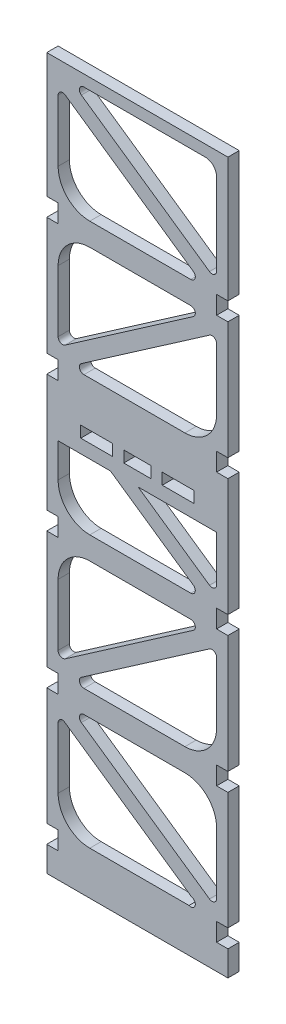
SolidWorks part; units mm, degrees
material "Balsa"
ref_plane "Front Plane" through (0, 0, 0) normal (0, 0, 1) x (1, 0, 0)
ref_plane "Top Plane" through (0, 0, 0) normal (0, 1, 0) x (1, 0, 0)
ref_plane "Right Plane" through (0, 0, 0) normal (1, 0, 0) x (0, 0, -1)
sketch "Model" plane through (0, 0, 0) normal (0, 0, 1) x (1, 0, 0)
  line L0 (77.47, 87.63) -> (20.8312, 87.63)
  line L1 (95.25, 35.3278) -> (95.25, 69.85)
  line L2 (19.3854, 83.0016) -> (91.2642, 33.2394)
  line L3 (6.35, 146.05) -> (6.35, 111.5278)
  line L4 (80.7688, 163.83) -> (24.13, 163.83)
  line L5 (10.3358, 109.4394) -> (82.2146, 159.2016)
  line L6 (77.47, 240.03) -> (20.8312, 240.03)
  line L7 (95.25, 187.7278) -> (95.25, 222.25)
  line L8 (19.3854, 235.4016) -> (91.2642, 185.6394)
  line L9 (24.13, 176.53) -> (80.7688, 176.53)
  line L10 (6.35, 228.8322) -> (6.35, 194.31)
  line L11 (82.2146, 181.1584) -> (10.3358, 230.9206)
  line L12 (91.2642, 154.7206) -> (19.3854, 104.9584)
  line L13 (95.25, 118.11) -> (95.25, 152.6322)
  line L14 (20.8312, 100.33) -> (77.47, 100.33)
  line L15 (6.35, 298.45) -> (6.35, 263.9278)
  line L16 (80.7688, 316.23) -> (24.13, 316.23)
  line L17 (10.3358, 261.8394) -> (82.2146, 311.6016)
  line L18 (88.9, 392.43) -> (20.8312, 392.43)
  line L19 (95.25, 340.1278) -> (95.25, 386.08)
  line L20 (19.3854, 387.8016) -> (91.2642, 338.0394)
  line L21 (24.13, 328.93) -> (80.7688, 328.93)
  line L22 (6.35, 381.2322) -> (6.35, 346.71)
  line L23 (82.2146, 333.5584) -> (10.3358, 383.3206)
  line L24 (24.13, 24.3357) -> (79.7674, 24.3357)
  line L25 (6.35, 76.4322) -> (6.35, 42.1157)
  line L26 (81.3163, 29.1503) -> (9.4375, 78.9125)
  line L27 (91.2642, 307.1206) -> (19.3854, 257.3584)
  line L28 (95.25, 270.51) -> (95.25, 305.0322)
  line L29 (20.8312, 252.73) -> (77.47, 252.73)
  line L30 (0, 398.78) -> (0, 0)
  line L31 (0, 0) -> (101.6, 0)
  line L32 (101.6, 398.78) -> (101.6, 0)
  line L33 (0, 398.78) -> (101.6, 398.78)
  arc A1 (91.2642, 33.2394) -> (95.25, 35.3278) centre (92.71, 35.3278) ccw
  arc A2 (20.8312, 87.63) -> (19.3854, 83.0016) centre (20.8312, 85.09) ccw
  arc A4 (82.2146, 159.2016) -> (80.7688, 163.83) centre (80.7688, 161.29) ccw
  arc A5 (6.35, 111.5278) -> (10.3358, 109.4394) centre (8.89, 111.5278) ccw
  arc A7 (91.2642, 185.6394) -> (95.25, 187.7278) centre (92.71, 187.7278) ccw
  arc A8 (20.8312, 240.03) -> (19.3854, 235.4016) centre (20.8312, 237.49) ccw
  arc A10 (10.3358, 230.9206) -> (6.35, 228.8322) centre (8.89, 228.8322) ccw
  arc A11 (80.7688, 176.53) -> (82.2146, 181.1584) centre (80.7688, 179.07) ccw
  arc A12 (95.25, 152.6322) -> (91.2642, 154.7206) centre (92.71, 152.6322) ccw
  arc A14 (19.3854, 104.9584) -> (20.8312, 100.33) centre (20.8312, 102.87) ccw
  arc A16 (82.2146, 311.6016) -> (80.7688, 316.23) centre (80.7688, 313.69) ccw
  arc A17 (6.35, 263.9278) -> (10.3358, 261.8394) centre (8.89, 263.9278) ccw
  arc A18 (95.25, 386.08) -> (88.9, 392.43) centre (88.9, 386.08) ccw
  arc A19 (91.2642, 338.0394) -> (95.25, 340.1278) centre (92.71, 340.1278) ccw
  arc A20 (20.8312, 392.43) -> (19.3854, 387.8016) centre (20.8312, 389.89) ccw
  arc A22 (10.3358, 383.3206) -> (6.35, 381.2322) centre (8.89, 381.2322) ccw
  arc A23 (80.7688, 328.93) -> (82.2146, 333.5584) centre (80.7688, 331.47) ccw
  arc A25 (9.4375, 78.9125) -> (6.35, 76.4322) centre (8.89, 76.4322) ccw
  arc A26 (79.7674, 24.3357) -> (81.3163, 29.1503) centre (80.7688, 26.67) ccw
  arc A27 (95.25, 305.0322) -> (91.2642, 307.1206) centre (92.71, 305.0322) ccw
  arc A29 (19.3854, 257.3584) -> (20.8312, 252.73) centre (20.8312, 255.27) ccw
  arc A30 (6.35, 42.1157) -> (24.13, 24.3357) centre (24.13, 42.1157) ccw
  arc A31 (6.35, 346.71) -> (24.13, 328.93) centre (24.13, 346.71) ccw
  arc A32 (6.35, 298.45) -> (24.13, 316.23) centre (24.13, 298.45) cw
  arc A33 (95.25, 270.51) -> (77.47, 252.73) centre (77.47, 270.51) cw
  arc A34 (77.47, 240.03) -> (95.25, 222.25) centre (77.47, 222.25) cw
  arc A35 (6.35, 194.31) -> (24.13, 176.53) centre (24.13, 194.31) ccw
  arc A36 (6.35, 146.05) -> (24.13, 163.83) centre (24.13, 146.05) cw
  arc A37 (77.47, 100.33) -> (95.25, 118.11) centre (77.47, 118.11) ccw
  arc A38 (77.47, 87.63) -> (95.25, 69.85) centre (77.47, 69.85) cw
  dimension "D3" = 6.35
  dimension "D4" = 2.54
  dimension "D5" = 2.54
  dimension "D6" = 2.54
  dimension "D7" = 2.54
  dimension "D8" = 2.54
  dimension "D9" = 2.54
  dimension "D10" = 2.54
  dimension "D11" = 2.54
  dimension "D12" = 2.54
  dimension "D13" = 2.54
  dimension "D14" = 2.54
  dimension "D15" = 2.54
  dimension "D16" = 2.54
  dimension "D17" = 2.54
  dimension "D18" = 2.54
  dimension "D19" = 2.54
  dimension "D20" = 2.54
  dimension "D21" = 2.54
  dimension "D22" = 2.54
  dimension "D26" = 17.78
  dimension "D27" = 17.78
  dimension "D1" = 398.78
  dimension "D2" = 101.6
  dimension "D23" = 26.67
  dimension "D24" = 20.8312
  dimension "D25" = 87.4233
extrude "Boss-Extrude1" add sketch "Model" along normal blind 6.35
sketch "Sketch1" plane through (0, 0, 6.35) normal (0, 0, 1) x (1, 0, 0)
  line L0 (101.6, 0) -> (101.6, 398.78) construction
  line L1 (101.6, 328.93) -> (95.25, 328.93)
  line L2 (101.6, 328.93) -> (101.6, 318.77)
  line L3 (101.6, 318.77) -> (95.25, 318.77)
  line L4 (95.25, 328.93) -> (95.25, 318.77)
  line L5 (0, 398.78) -> (0, 0) construction
  line L6 (0, 252.73) -> (6.35, 252.73)
  line L7 (0, 252.73) -> (0, 242.57)
  line L8 (0, 242.57) -> (6.35, 242.57)
  line L9 (6.35, 252.73) -> (6.35, 242.57)
  line L10 (24.13, 328.93) -> (80.7688, 328.93) construction
  line L11 (101.6, 176.53) -> (95.25, 176.53)
  line L12 (101.6, 176.53) -> (101.6, 166.37)
  line L13 (101.6, 166.37) -> (95.25, 166.37)
  line L14 (95.25, 176.53) -> (95.25, 166.37)
  line L15 (0, 100.33) -> (6.35, 100.33)
  line L16 (0, 100.33) -> (0, 90.17)
  line L17 (0, 90.17) -> (6.35, 90.17)
  line L18 (6.35, 100.33) -> (6.35, 90.17)
  line L19 (20.8312, 252.73) -> (77.47, 252.73) construction
  line L21 (20.8312, 100.33) -> (77.47, 100.33) construction
  line L22 (24.13, 24.3357) -> (79.7674, 24.3357) construction
  line L23 (0, 328.93) -> (6.35, 328.93)
  line L24 (0, 328.93) -> (0, 318.77)
  line L25 (0, 318.77) -> (6.35, 318.77)
  line L26 (6.35, 328.93) -> (6.35, 318.77)
  line L27 (101.6, 252.73) -> (95.25, 252.73)
  line L28 (101.6, 252.73) -> (101.6, 242.57)
  line L29 (101.6, 242.57) -> (95.25, 242.57)
  line L30 (95.25, 252.73) -> (95.25, 242.57)
  line L31 (0, 176.53) -> (6.35, 176.53)
  line L32 (0, 176.53) -> (0, 166.37)
  line L33 (0, 166.37) -> (6.35, 166.37)
  line L34 (6.35, 176.53) -> (6.35, 166.37)
  line L35 (101.6, 100.33) -> (95.25, 100.33)
  line L36 (101.6, 100.33) -> (101.6, 90.17)
  line L37 (101.6, 90.17) -> (95.25, 90.17)
  line L38 (95.25, 100.33) -> (95.25, 90.17)
  line L39 (0, 24.3357) -> (6.35, 24.3357)
  line L40 (0, 24.3357) -> (0, 14.1757)
  line L41 (0, 14.1757) -> (6.35, 14.1757)
  line L42 (6.35, 24.3357) -> (6.35, 14.1757)
  line L43 (101.6, 24.3357) -> (95.25, 24.3357)
  line L44 (101.6, 24.3357) -> (101.6, 14.1757)
  line L45 (101.6, 14.1757) -> (95.25, 14.1757)
  line L46 (95.25, 24.3357) -> (95.25, 14.1757)
  line L47 (24.13, 176.53) -> (80.7688, 176.53) construction
  dimension "D1" = 6.35
  dimension "D2" = 10.16
  dimension "D3" = 10.16
  dimension "D4" = 6.35
  dimension "D5" = 6.35
  dimension "D6" = 10.16
  dimension "D7" = 6.35
  dimension "D8" = 10.16
  dimension "D9" = 10.16
  dimension "D10" = 10.16
extrude "Cut-Extrude1" cut sketch "Sketch1" against normal up to surface (6.35 mm away) contours L1 L4 L3 L2 | L27 L30 L29 L28 | L9 L6 L7 L8 | L42 L39 L40 L41 | L11 L14 L13 L12 | L26 L25 L24 L23 | L43 L46 L45 L44 | L38 L37 L36 L35 | L15 L18 L17 L16 | L31 L34 L33 L32 region at (98.425, 323.85, 6.35) region at (3.175, 247.65, 6.35) region at (98.425, 171.45, 6.35) region at (98.425, 247.65, 6.35) region at (3.175, 19.2557, 6.35) up to face at (50.8, 199.39, 0)
sketch "Sketch3" plane through (0, 0, 6.35) normal (0, 0, 1) x (1, 0, 0)
  line L0 (101.6, 176.53) -> (101.6, 242.57) construction
  line L1 (101.6, 213.36) -> (0, 213.36)
  line L2 (101.6, 213.36) -> (101.6, 242.57)
  line L3 (101.6, 242.57) -> (0, 242.57)
  line L4 (0, 213.36) -> (0, 242.57)
  line L5 (24.13, 176.53) -> (80.7688, 176.53) construction
  point P4 (0, 242.57)
  point P6 (0, 0)
  point P7 (101.6, 184.181)
  dimension "D1" = 36.83
extrude "Boss-Extrude2" add sketch "Sketch3" against normal up to surface (6.35 mm away) up to face at (50.8, 174.0274, 0)
sketch "Sketch4" plane through (0, 0, 6.35) normal (0, 0, 1) x (1, 0, 0)
  line L0 (6.35, 213.36) -> (35.7011, 213.36) construction
  line L1 (82.55, 220.98) -> (64.77, 220.98)
  line L2 (82.55, 220.98) -> (82.55, 227.33)
  line L3 (82.55, 227.33) -> (64.77, 227.33)
  line L4 (64.77, 220.98) -> (64.77, 227.33)
  line L5 (58.42, 220.98) -> (43.18, 220.98)
  line L6 (58.42, 220.98) -> (58.42, 227.33)
  line L7 (58.42, 227.33) -> (43.18, 227.33)
  line L8 (43.18, 220.98) -> (43.18, 227.33)
  line L9 (36.83, 220.98) -> (19.05, 220.98)
  line L10 (36.83, 220.98) -> (36.83, 227.33)
  line L11 (36.83, 227.33) -> (19.05, 227.33)
  line L12 (19.05, 220.98) -> (19.05, 227.33)
  line L13 (0, 242.57) -> (0, 176.53) construction
  point P14 (36.83, 224.155)
  dimension "D1" = 6.35
  dimension "D2" = 7.62
  dimension "D3" = 17.78
  dimension "D4" = 15.24
  dimension "D5" = 17.78
  dimension "D6" = 6.35
  dimension "D7" = 6.35
  dimension "D8" = 19.05
extrude "Cut-Extrude2" cut sketch "Sketch4" against normal up to surface (6.35 mm away) up to face at (83.4048, 199.7204, 0)
equation "\"thick\"=0.25"
equation "\"D1@Boss-Extrude1\"=\"thick\""
